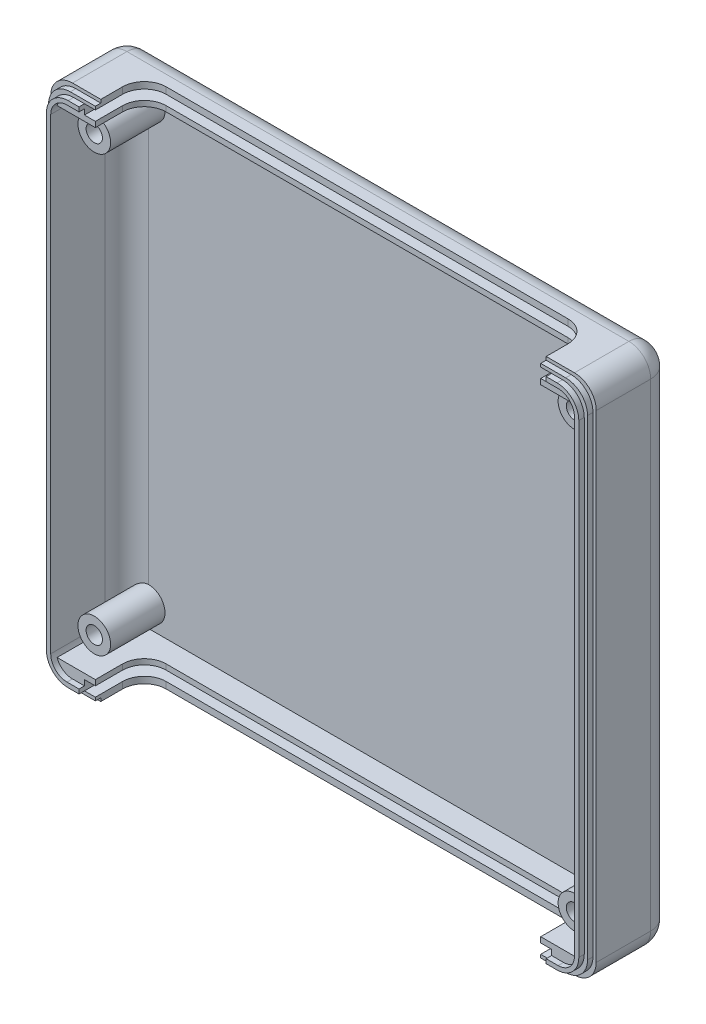
SolidWorks part; units mm, degrees
ref_plane "Спереди" through (0, 0, 0) normal (0, 0, 1) x (1, 0, 0)
ref_plane "Сверху" through (0, 0, 0) normal (0, 1, 0) x (1, 0, 0)
ref_plane "Справа" through (0, 0, 0) normal (1, 0, 0) x (0, 0, -1)
sketch "Эскиз3" plane through (0, 0, 0) normal (0, 0, 1) x (1, 0, 0)
  line L1 (50.1, 47.9) -> (-50.1, 47.9)
  line L2 (50.1, 47.9) -> (50.1, -47.9)
  line L3 (50.1, -47.9) -> (-50.1, -47.9)
  line L4 (-50.1, 47.9) -> (-50.1, -47.9)
  line L5 (50.1, 47.9) -> (-50.1, -47.9) construction
  line L6 (50.1, -47.9) -> (-50.1, 47.9) construction
  point P0 (0, 0)
  dimension "D1" = 95.8
  dimension "D2" = 100.2
extrude "Бобышка-Вытянуть1" add sketch "Эскиз3" against normal blind 2
sketch "Эскиз4" plane through (0, 0, -2) normal (0, 0, -1) x (-1, 0, 0)
  line L1 (-50.1, 47.9) -> (50.1, 47.9)
  line L2 (-50.1, 47.9) -> (-50.1, -47.9)
  line L3 (-50.1, -47.9) -> (50.1, -47.9)
  line L4 (50.1, 47.9) -> (50.1, -47.9)
  line L5 (-48.1, 43.9) -> (48.1, 43.9)
  line L6 (-48.1, 43.9) -> (-48.1, -43.9)
  line L7 (-48.1, -43.9) -> (48.1, -43.9)
  line L8 (48.1, 43.9) -> (48.1, -43.9)
  dimension "D1" = 2
  dimension "D2" = 4
  dimension "D3" = 4
  dimension "D4" = 2
extrude "Бобышка-Вытянуть2" add sketch "Эскиз4" against normal blind 14
sketch "Эскиз5" plane through (0, 0, 12) normal (0, 0, 1) x (1, 0, 0)
  line L0 (-50.1, -47.9) -> (-50.1, 47.9) construction
  line L1 (-49.5, 47.3) -> (49.5, 47.3)
  line L2 (-49.5, 47.3) -> (-49.5, -47.3)
  line L3 (-49.5, -47.3) -> (49.5, -47.3)
  line L4 (49.5, 47.3) -> (49.5, -47.3)
  line L5 (50.1, 47.9) -> (50.1, -47.9) construction
  line L6 (50.1, -47.9) -> (-50.1, -47.9) construction
  line L7 (-48.1, 43.9) -> (48.1, 43.9)
  line L8 (-48.1, 43.9) -> (-48.1, -43.9)
  line L9 (-48.1, -43.9) -> (48.1, -43.9)
  line L10 (48.1, 43.9) -> (48.1, -43.9)
  line L11 (-50.1, 47.9) -> (50.1, 47.9) construction
  dimension "D1" = 0.6
  dimension "D2" = 0.6
  dimension "D3" = 0.6
  dimension "D4" = 0.6
extrude "Бобышка-Вытянуть3" add sketch "Эскиз5" along normal blind 1
sketch "Эскиз6" plane through (0, 0, 13) normal (0, 0, 1) x (1, 0, 0)
  line L0 (-49.5, 47.3) -> (-49.5, -47.3) construction
  line L1 (-48.1, 43.9) -> (48.1, 43.9)
  line L2 (-48.1, 43.9) -> (-48.1, -43.9)
  line L3 (-48.1, -43.9) -> (48.1, -43.9)
  line L4 (48.1, 43.9) -> (48.1, -43.9)
  line L5 (-48.9, 46.7) -> (48.9, 46.7)
  line L6 (-48.9, 46.7) -> (-48.9, -46.7)
  line L7 (-48.9, -46.7) -> (48.9, -46.7)
  line L8 (48.9, 46.7) -> (48.9, -46.7)
  line L9 (49.5, -47.3) -> (49.5, 47.3) construction
  line L10 (-49.5, -47.3) -> (49.5, -47.3) construction
  line L11 (49.5, 47.3) -> (-49.5, 47.3) construction
  dimension "D1" = 0.6
  dimension "D2" = 0.6
  dimension "D3" = 0.6
  dimension "D4" = 0.6
extrude "Бобышка-Вытянуть4" add sketch "Эскиз6" along normal blind 1
sketch "Эскиз10" plane through (0, 0, 14) normal (0, 0, 1) x (1, 0, 0)
  line L0 (-48.1, -43.9) -> (48.1, -43.9) construction
  line L1 (-42.9, -43.9) -> (42.9, -43.9)
  line L2 (-42.9, -43.9) -> (-42.9, -46.7)
  line L3 (-42.9, -46.7) -> (42.9, -46.7)
  line L4 (42.9, -43.9) -> (42.9, -46.7)
  line L5 (-48.9, -46.7) -> (48.9, -46.7) construction
  line L6 (48.1, -43.9) -> (48.1, 43.9) construction
  line L7 (-48.1, 43.9) -> (-48.1, -43.9) construction
  dimension "D1" = 5.2
  dimension "D2" = 5.2
extrude "Вырез-Вытянуть3" cut sketch "Эскиз10" against normal blind 1
sketch "Эскиз11" plane through (0, 0, 14) normal (0, 0, 1) x (1, 0, 0)
  line L1 (-42.9, -44.9) -> (42.9, -44.9)
  line L2 (-42.9, -44.9) -> (-42.9, -46.7)
  line L3 (-42.9, -46.7) -> (42.9, -46.7)
  line L4 (42.9, -44.9) -> (42.9, -46.7)
  line L6 (50.1, -47.9) -> (-50.1, -47.9) construction
  line L7 (42.9, -43.9) -> (-42.9, -43.9) construction
  line L8 (-48.9, 46.7) -> (-48.9, -46.7) construction
  line L9 (48.9, -46.7) -> (48.9, 46.7) construction
  dimension "D1" = 6
  dimension "D2" = 6
  dimension "D3" = 1.2
  dimension "D4" = 1
extrude "Вырез-Вытянуть4" cut sketch "Эскиз11" against normal blind 12
sketch "Эскиз12" plane through (0, 0, 14) normal (0, 0, 1) x (1, 0, 0)
  line L0 (48.1, -43.9) -> (-48.1, -43.9) construction
  line L1 (-40.9, -43.9) -> (40.9, -43.9)
  line L2 (-40.9, -43.9) -> (-40.9, -47.9)
  line L3 (-40.9, -47.9) -> (40.9, -47.9)
  line L4 (40.9, -43.9) -> (40.9, -47.9)
  line L5 (-48.1, -43.9) -> (-42.9, -43.9) construction
  line L6 (50.1, -47.9) -> (-50.1, -47.9) construction
  line L9 (-42.9, -43.9) -> (-42.9, -46.7) construction
  line L10 (42.9, -46.7) -> (42.9, -43.9) construction
  dimension "D1" = 2
  dimension "D2" = 2
extrude "Вырез-Вытянуть6" cut sketch "Эскиз12" against normal blind 10
mirror "Зеркальное отражение9" about plane through (0, 0, 0) normal (0, 1, 0) of "Вырез-Вытянуть3"
mirror "Зеркальное отражение10" about plane through (0, 0, 0) normal (0, 1, 0) of "Вырез-Вытянуть4"
mirror "Зеркальное отражение11" about plane through (0, 0, 0) normal (0, 1, 0) of "Вырез-Вытянуть6"
sketch "Эскиз15" plane through (0, 0, 0) normal (0, 0, 1) x (1, 0, 0)
  line L0 (-48.1, -43.9) -> (-42.9, -43.9) construction
  line L1 (-48.1, -43.9) -> (-48.1, 43.9) construction
  circle A0 centre (-44.1, -39.9) radius 3
  point P0 (-44.1, -39.9)
  dimension "D3" = 6
  dimension "D1" = 4
  dimension "D2" = 4
extrude "Бобышка-Вытянуть5" add sketch "Эскиз15" along normal blind 10
sketch "Эскиз16" plane through (0, 0, 10) normal (0, 0, 1) x (1, 0, 0)
  circle A0 centre (-44.1, -39.9) radius 1.5
  dimension "D1" = 3
extrude "Вырез-Вытянуть10" cut sketch "Эскиз16" against normal blind 9
mirror "Зеркальное отражение13" about plane through (0, 0, 0) normal (1, 0, 0) of "Бобышка-Вытянуть5"
mirror "Зеркальное отражение14" about plane through (0, 0, 0) normal (0, 1, 0) of "Бобышка-Вытянуть5", "Зеркальное отражение13"
mirror "Зеркальное отражение15" about plane through (0, 0, 0) normal (1, 0, 0) of "Вырез-Вытянуть10"
mirror "Зеркальное отражение16" about plane through (0, 0, 0) normal (0, 1, 0) of "Зеркальное отражение15", "Вырез-Вытянуть10"
sketch "Эскиз17" plane through (0, 0, -2) normal (0, 0, -1) x (-1, 0, 0)
  circle A0 centre (-44.1, -39.9) radius 2.1
  dimension "D1" = 4.2
extrude "Вырез-Вытянуть11" cut sketch "Эскиз17" against normal blind 8
mirror "Зеркальное отражение17" about plane through (0, 0, 0) normal (1, 0, 0) of "Вырез-Вытянуть11"
mirror "Зеркальное отражение18" about plane through (0, 0, 0) normal (0, 1, 0) of "Вырез-Вытянуть11", "Зеркальное отражение17"
sketch "Эскиз22" plane through (0, 0, 14) normal (0, 0, 1) x (1, 0, 0)
  line L0 (-48.9, -46.7) -> (-42.9, -46.7) construction
  line L1 (-48.1, -43.9) -> (48.1, -43.9)
  line L2 (-48.1, -43.9) -> (-48.1, -45.9)
  line L3 (-48.1, -45.9) -> (48.1, -45.9)
  line L4 (48.1, -43.9) -> (48.1, -45.9)
  line L5 (48.9, -46.7) -> (48.9, 46.7) construction
  dimension "D1" = 0.8
  dimension "D2" = 0.8
extrude "Вырез-Вытянуть13" cut sketch "Эскиз22" against normal blind 1
fillet "Скругление7" radius 3 1 edges at (-48.1, -45.9, 13.5)
fillet "Скругление10" radius 3 1 edges at (48.1, -45.9, 13.5)
mirror "Зеркальное отражение19" about plane through (0, 0, 0) normal (0, 1, 0) of "Скругление10", "Скругление7", "Вырез-Вытянуть13"
fillet "Скругление4" radius 4 8 edges at (-40.9, 44.4, 4) (-40.9, 47.3, 4) (40.9, 44.4, 4) (40.9, 47.3, 4) (40.9, -44.4, 4) (40.9, -47.3, 4) (-40.9, -44.4, 4) (-40.9, -47.3, 4)
fillet "Скругление12" radius 4 16 edges at (0, -47.9, -2) (-50.1, 0, -2) (0, 47.9, -2) (50.1, 0, -2) (50.1, 47.9, 5) (49.5, 47.3, 12.5) (48.9, 46.7, 13.5) (50.1, -47.9, 5) (49.5, -47.3, 12.5) (48.9, -46.7, 13.5) (-50.1, -47.9, 5) (-49.5, -47.3, 12.5) (-48.9, -46.7, 13.5) (-50.1, 47.9, 5) (-49.5, 47.3, 12.5) (-48.9, 46.7, 13.5)
fillet "Скругление14" radius 4 6 edges at (-48.0568, -43.4073, 0) (-48.0568, 43.4073, 0) (48.0568, 43.4073, 0) (48.0568, -43.4073, 0) (-48.1, 0, 0) (48.1, 0, 0)
